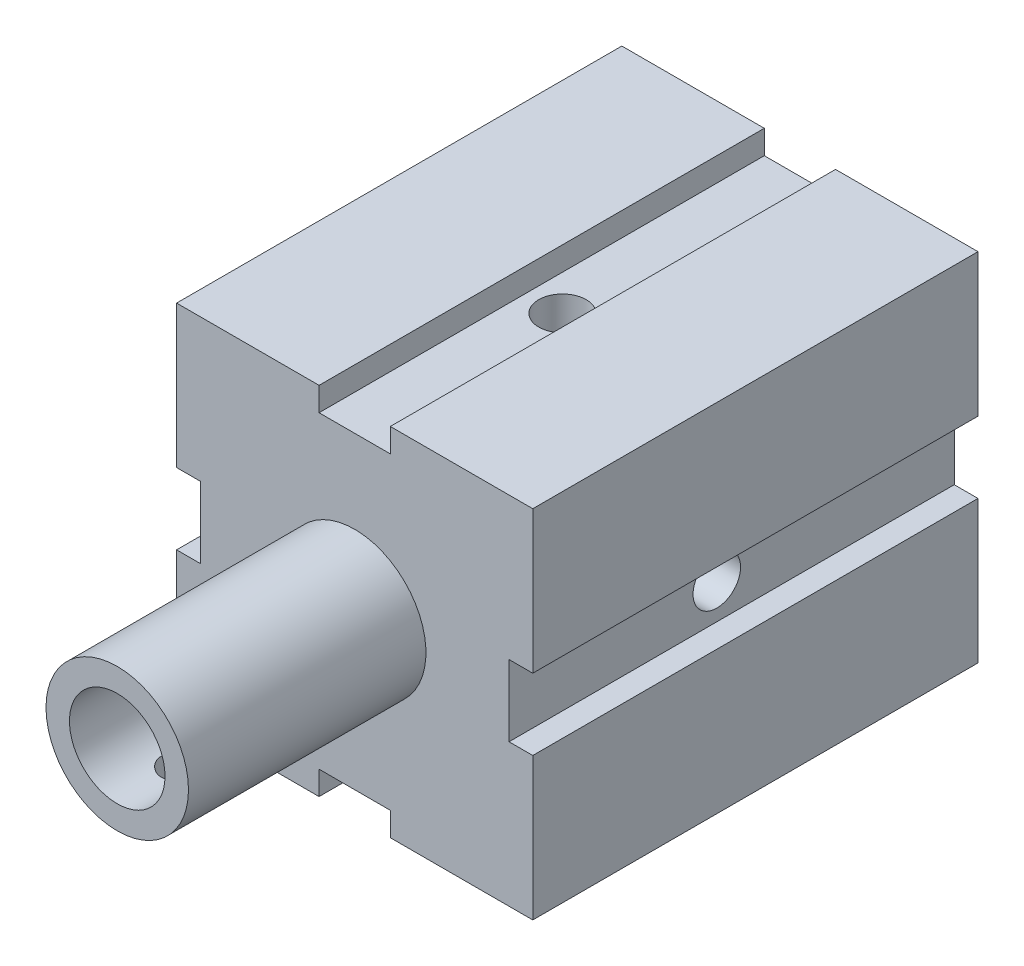
SolidWorks part; units mm, degrees
ref_plane "Front Plane" through (0, 0, 0) normal (0, 0, 1) x (1, 0, 0)
ref_plane "Top Plane" through (0, 0, 0) normal (0, 1, 0) x (1, 0, 0)
ref_plane "Right Plane" through (0, 0, 0) normal (1, 0, 0) x (0, 0, -1)
sketch "Sketch1" plane through (0, 0, 0) normal (0, 0, 1) x (1, 0, 0)
  line L1 (302.8649, 107.5498) -> (332.8649, 107.5498)
  line L2 (302.8649, 107.5498) -> (302.8649, 77.5498)
  line L3 (302.8649, 77.5498) -> (332.8649, 77.5498)
  line L4 (332.8649, 107.5498) -> (332.8649, 77.5498)
  dimension "D1" = 30
  dimension "D2" = 30
extrude "Boss-Extrude1" add sketch "Sketch1" along normal blind 37.5 contours L2 L3 L4 L1
sketch "Sketch2" plane through (0, 0, 37.5) normal (0, 0, 1) x (1, 0, 0)
  line L0 (317.8649, 77.5498) -> (317.8649, 107.5498) construction
  line L1 (302.8649, 77.5498) -> (332.8649, 77.5498) construction
  line L2 (302.8649, 107.5498) -> (332.8649, 107.5498) construction
  circle A0 centre (317.8649, 92.5498) radius 6
  circle A1 centre (317.8649, 92.5498) radius 4.025
extrude "Boss-Extrude2" add sketch "Sketch2" along normal blind 20
sketch "Sketch3" plane through (0, 0, 37.5) normal (0, 0, 1) x (1, 0, 0)
  circle A0 centre (317.8649, 92.5498) radius 4.025
extrude "Cut-Extrude1" cut sketch "Sketch3" against normal blind 10
sketch "Sketch4" plane through (0, 77.5498, 0) normal (0, -1, 0) x (1, 0, 0)
  line L0 (302.8649, 0) -> (332.8649, 0) construction
  line L1 (314.8649, -37.5) -> (320.8649, -37.5)
  line L2 (314.8649, -37.5) -> (314.8649, 37.5)
  line L3 (314.8649, 37.5) -> (320.8649, 37.5)
  line L4 (320.8649, -37.5) -> (320.8649, 37.5)
  line L5 (314.8649, -37.5) -> (320.8649, 37.5) construction
  line L6 (314.8649, 37.5) -> (320.8649, -37.5) construction
  line L7 (302.8649, 37.5) -> (332.8649, 37.5) construction
  point P0 (317.8649, 0)
  dimension "D1" = 6
extrude "Cut-Extrude2" cut sketch "Sketch4" against normal blind 2
pattern_circular "CirPattern1" count 4 over 360 about axis through (317.8649, 92.5498, 27.5) along (0, 0, 1) of "Cut-Extrude2"
sketch "Sketch5" plane through (330.8649, 0, 0) normal (1, 0, 0) x (0, 0, -1)
  line L0 (-37.5, 92.5498) -> (0, 92.5498) construction
  line L1 (-37.5, 95.5498) -> (-37.5, 89.5498) construction
  line L2 (0, 89.5498) -> (0, 95.5498) construction
  circle A0 centre (-20, 92.5498) radius 2
  dimension "D1" = 20
extrude "Cut-Extrude3" cut sketch "Sketch5" against normal through all
sketch "Sketch6" plane through (0, 79.5498, 0) normal (0, -1, 0) x (1, 0, 0)
  line L0 (317.8649, 37.5) -> (317.8649, 0) construction
  line L1 (320.8649, 37.5) -> (314.8649, 37.5) construction
  line L2 (314.8649, 0) -> (320.8649, 0) construction
  circle A0 centre (317.8649, 20) radius 2
  dimension "D1" = 20
extrude "Cut-Extrude4" cut sketch "Sketch6" against normal through all
hole_wizard "M3x0.5 Tapped Hole1" positions "3DSketch1" profile "Sketch7" tap size "M3x0.5" standard "ANSI Metric" end condition up to next
sketch3d "3DSketch1"
  point P0 (317.712, 86.5517, 43.6128)
  point P2 (317.6684, 86.553, 52.4548)
sketch "Sketch7" plane through (317.712, 86.5517, 43.6128) normal (0, 0, 1) x (0.9997, -0.0255, 0)
  line L0 (0, 0) -> (0, 1.975)
  line L1 (0, 1.975) -> (1.25, 1.975)
  line L2 (1.25, 1.975) -> (1.25, 0)
  line L5 (1.25, 0) -> (0, 0)
  line L11 (0, -6.35) -> (0, 107.95) construction
  dimension "Thru Tap Drill Dia." = 2.5
  dimension "Thru Tap Drill Depth" = 1.975
cosmetic thread "Hole Thread1" parameters "D2"=3
cosmetic thread "Hole Thread2" parameters "D2"=3
